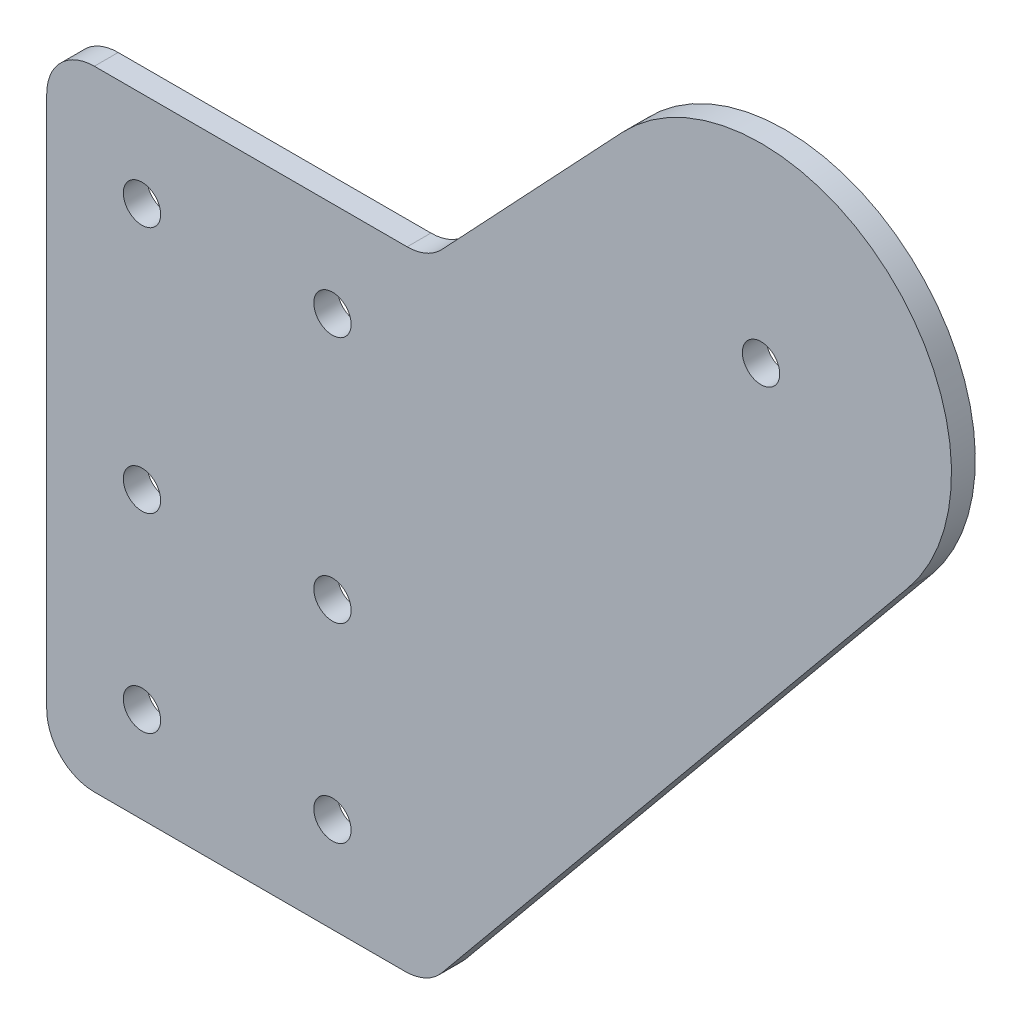
SolidWorks part; units mm, degrees
material "6061-T6 (SS)"
ref_plane "Front Plane" through (0, 0, 0) normal (0, 0, 1) x (1, 0, 0)
ref_plane "Top Plane" through (0, 0, 0) normal (0, 1, 0) x (1, 0, 0)
ref_plane "Right Plane" through (0, 0, 0) normal (1, 0, 0) x (0, 0, -1)
sketch "Sketch2" plane through (0, 0, 0) normal (0, 0, 1) x (1, 0, 0)
  line L0 (50.8, 83.82) -> (76.7561, 111.3908)
  line L1 (0, 0) -> (50.8, 0)
  line L2 (0, 0) -> (0, 83.82)
  line L3 (0, 83.82) -> (50.8, 83.82)
  line L5 (50.8, 0) -> (114.8621, 77.8392)
  arc A1 (114.8621, 77.8392) -> (76.7561, 111.3908) centre (95.25, 93.98) ccw
  circle A2 centre (95.25, 93.98) radius 2.4892
  dimension "D3" = 50.8
  dimension "D5" = 95.25
  dimension "D4" = 4.9784
  dimension "D1" = 50.8
  dimension "D2" = 83.82
  dimension "D6" = 93.98
extrude "Boss-Extrude1" add sketch "Sketch2" against normal blind 3.175
sketch "Sketch3" plane through (0, 0, 0) normal (0, 0, 1) x (1, 0, 0)
  line L0 (50.8, 83.82) -> (0, 83.82) construction
  line L1 (0, 83.82) -> (0, 0) construction
  circle A0 centre (12.7, 71.12) radius 2.4892
  circle A17 centre (38.1, 71.12) radius 2.4892
  circle A24 centre (12.7, 38.1) radius 2.4892
  circle A25 centre (12.7, 12.7) radius 2.4892
  circle A26 centre (12.7, -12.7) radius 2.4892
  circle A27 centre (12.7, -38.1) radius 2.4892
  circle A28 centre (12.7, -63.5) radius 2.4892
  circle A33 centre (38.1, 12.7) radius 2.4892
  circle A34 centre (38.1, -12.7) radius 2.4892
  circle A35 centre (38.1, -38.1) radius 2.4892
  circle A36 centre (38.1, -63.5) radius 2.4892
  circle A41 centre (38.1, 38.1) radius 2.4892
  dimension "D1" = 4.9784
  dimension "D6" = 4.9784
  dimension "D2" = 12.7
  dimension "D3" = 12.7
  dimension "D7" = 12.7
  dimension "D8" = 33.02
  dimension "D4" = 1
  dimension "D5" = 2
  dimension "D9" = 5
  dimension "D10" = 2
extrude "Cut-Extrude1" cut sketch "Sketch3" against normal through all
fillet "Fillet1" radius 6.35 4 edges at (0, 0, -1.5875) (50.8, 0, -1.5875) (50.8, 83.82, -1.5875) (0, 83.82, -1.5875)
